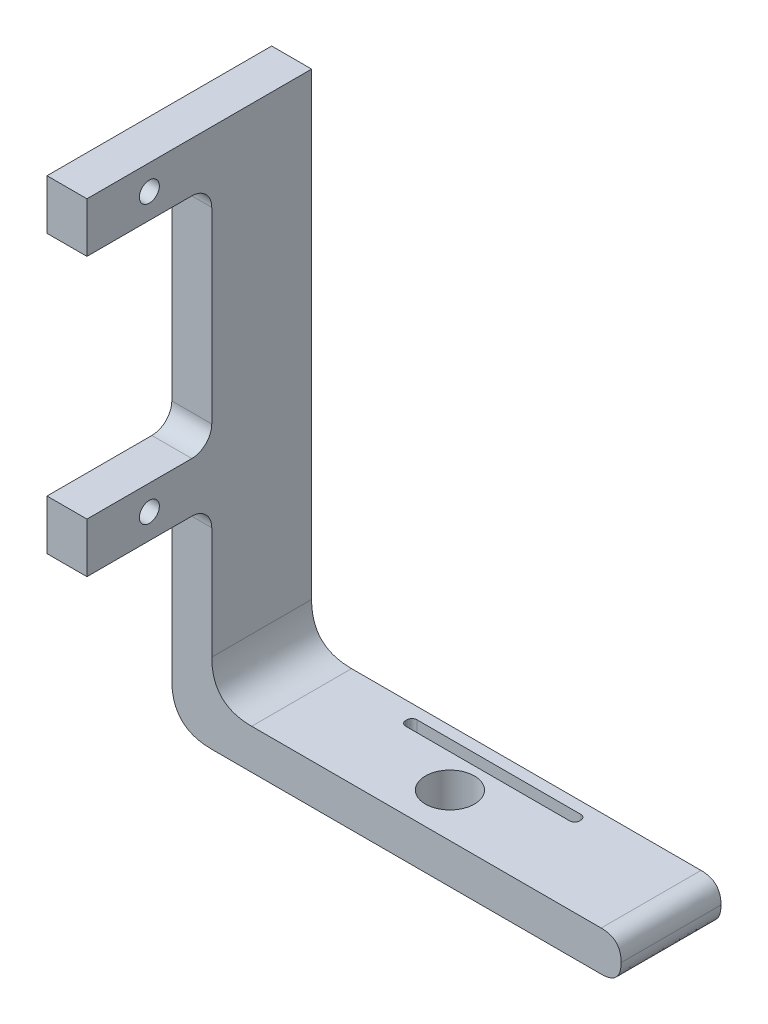
SolidWorks part; units mm, degrees
ref_plane "Спереди" through (0, 0, 0) normal (0, 0, 1) x (1, 0, 0)
ref_plane "Сверху" through (0, 0, 0) normal (0, 1, 0) x (1, 0, 0)
ref_plane "Справа" through (0, 0, 0) normal (1, 0, 0) x (0, 0, -1)
sketch "Эскиз1" plane through (0, 0, 0) normal (0, 0, 1) x (1, 0, 0)
  line L1 (0, 0) -> (45, 0)
  line L2 (0, 0) -> (0, 4)
  line L3 (0, 4) -> (45, 4)
  line L4 (45, 0) -> (45, 4)
  line L5 (0, 4) -> (4, 4)
  line L6 (0, 4) -> (0, 54)
  line L7 (0, 54) -> (4, 54)
  line L8 (4, 4) -> (4, 54)
  dimension "D1" = 50
  dimension "D2" = 4
  dimension "D3" = 4
  dimension "D4" = 45
extrude "Бобышка-Вытянуть1" add sketch "Эскиз1" along normal blind 10 contours L3 L8 L7 L6 | L1 L4 L3 L2 region at (22.5, 2, 0) region at (2, 29, 0)
sketch "Эскиз2" plane through (0, 0, 10) normal (0, 0, 1) x (1, 0, 0)
  line L0 (4, 4) -> (4, 54) construction
  line L1 (0, 54) -> (4, 54)
  line L2 (0, 54) -> (0, 49)
  line L3 (0, 49) -> (4, 49)
  line L4 (4, 54) -> (4, 49)
  line L5 (0, 0) -> (0, 54) construction
  line L6 (4, 21.22) -> (0, 21.22)
  line L7 (4, 21.22) -> (4, 26.22)
  line L8 (4, 26.22) -> (0, 26.22)
  line L9 (0, 21.22) -> (0, 26.22)
  point P14 (4, 23.72)
  point P21 (4, 51.5)
  dimension "D1" = 5
  dimension "D2" = 5
  dimension "D3" = 27.78
extrude "Бобышка-Вытянуть2" add sketch "Эскиз2" along normal blind 12.5
sketch "Эскиз3" plane through (4, 0, 0) normal (1, 0, 0) x (0, 0, -1)
  line L0 (-22.5, 49) -> (-10, 49) construction
  line L1 (-22.5, 26.22) -> (-10, 26.22) construction
  line L2 (-16.25, 54) -> (-16.25, 21.22) construction
  line L3 (-22.5, 54) -> (0, 54) construction
  line L4 (-22.5, 21.22) -> (-10, 21.22) construction
  line L5 (-22.5, 51.5) -> (-16.25, 51.5) construction
  line L6 (-22.5, 49) -> (-22.5, 54) construction
  line L7 (-22.5, 23.72) -> (-16.25, 23.72) construction
  line L8 (-22.5, 21.22) -> (-22.5, 26.22) construction
  circle A0 centre (-16.25, 51.5) radius 1
  circle A1 centre (-16.25, 23.72) radius 1
  point P0 (-16.25, 49)
  point P1 (-16.25, 26.22)
  point P23 (-16.25, 51.5)
  point P24 (-16.25, 23.72)
extrude "Вырез-Вытянуть1" cut sketch "Эскиз3" against normal up to surface (4 mm away) contours A0 | A1 up to face at (0, 30.088, 13)
fillet "Скругление1" radius 4 1 edges at (4, 4, 5) type face fillet first side face at (24.5, 4, 5) second side face at (4, 51.5, 15.25) conic rho 0.5
fillet "Скругление2" radius 4 1 edges at (0, 0, 5) type face fillet first side face at (0, 51.5, 17.25) second side face at (22.5, 0, 5) conic rho 0.5
fillet "Скругление3" radius 2 1 edges at (45, 4, 5) type face fillet first side face at (17.25, 4, 3.75) second side face at (45, 2, 5) conic rho 0.5
fillet "Скругление4" radius 2 1 edges at (45, 0, 5) type face fillet first side face at (45, 0.5, 3.75) second side face at (14.25, 0, 6.25) conic rho 0.5
sketch "Эскиз26" plane through (0, 4, 0) normal (0, 1, 0) x (1, 0, 0)
  circle A0 centre (23.4552, -5.6027) radius 2.45
  point P0 (23.4552, -5.6027)
sketch "Эскиз27" plane through (0, 4, 0) normal (0, 1, 0) x (1, 0, 0)
  circle A0 centre (23.4552, -5.6027) radius 1.5523
extrude "Вырез-Вытянуть2" cut sketch "Эскиз27" against normal blind 4 draft 7.86
fillet "Скругление5" radius 2 1 edges at (2, 49, 10) type face fillet first side face at (2, 49, 16.25) second side face at (2, 37.61, 10)
fillet "Скругление6" radius 2 1 edges at (2, 21.22, 10) type face fillet first side face at (2, 21.22, 16.25) second side face at (12.2222, 5.6911, 10)
fillet "Скругление7" radius 2 1 edges at (2, 26.22, 10) type face fillet first side face at (2, 36.61, 10) second side face at (2, 26.22, 16.25)
sketch "Эскиз32" plane through (0, 4, 0) normal (0, 1, 0) x (1, 0, 0)
  line L0 (15.2099, -1.1605) -> (32.6259, -1.1605)
  line L1 (15.2099, -2.2836) -> (32.6259, -2.2836)
  line L2 (15.2099, -1.1605) -> (15.2099, -2.2836)
  line L3 (32.6259, -1.1605) -> (32.6259, -2.2836)
  circle A0 centre (23.4552, -5.6027) radius 3
extrude "Вырез-Вытянуть3" cut sketch "Эскиз32" against normal blind 4 contours L3 L1 L2 L0
extrude "Cut-Extrude3" cut sketch "Эскиз26" against normal blind 10
fillet "Fillet1" radius 0.5 1 edges at (32.6259, 2, 1.1605) type face fillet first side face at (23.9179, 2, 1.1605) second side face at (32.6259, 2, 1.722)
fillet "Fillet2" radius 0.5 1 edges at (32.6259, 2, 2.2836) type face fillet first side face at (32.6259, 2, 1.972) second side face at (23.9179, 2, 2.2836)
fillet "Fillet3" radius 0.5 1 edges at (15.2099, 2, 1.1605) type face fillet first side face at (23.6679, 2, 1.1605) second side face at (15.2099, 2, 1.722)
fillet "Fillet4" radius 0.5 1 edges at (15.2099, 2, 2.2836) type face fillet first side face at (15.2099, 2, 1.972) second side face at (23.6679, 2, 2.2836)
